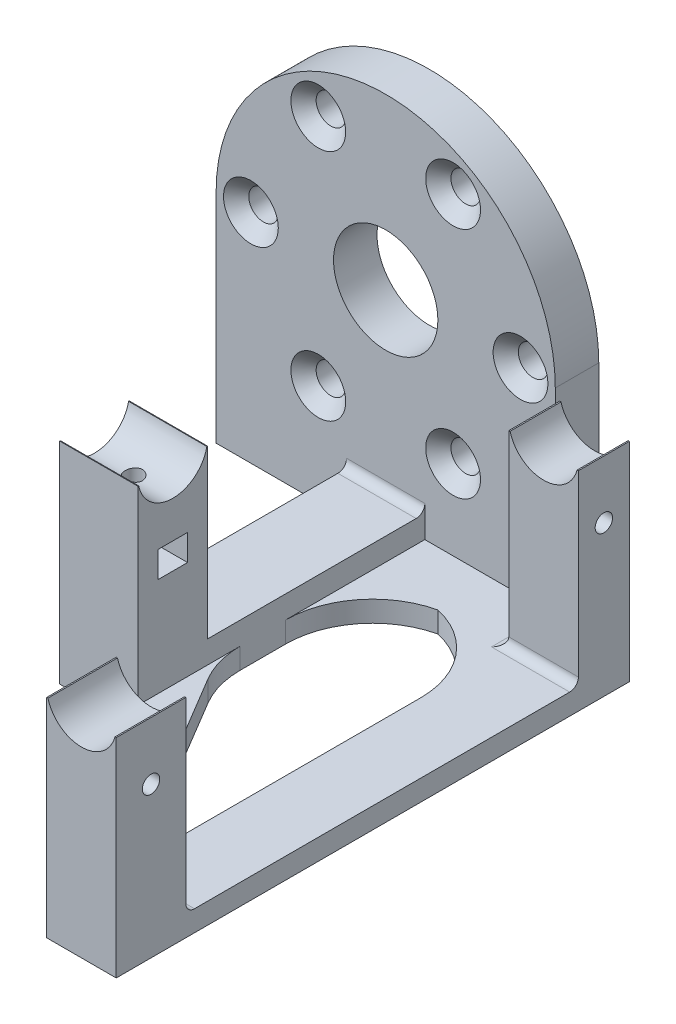
SolidWorks part; units mm, degrees
ref_plane "Front Plane" through (0, 0, 0) normal (0, 0, 1) x (1, 0, 0)
ref_plane "Top Plane" through (0, 0, 0) normal (0, 1, 0) x (1, 0, 0)
ref_plane "Right Plane" through (0, 0, 0) normal (1, 0, 0) x (0, 0, -1)
sketch "Sketch5" plane through (0, 0, 0) normal (0, 0, 1) x (1, 0, 0)
  line L0 (0, 0) -> (0, 15.5) construction
  circle A0 centre (0, 0) radius 19.5
  circle A1 centre (-7.75, 13.4234) radius 1.5
  circle A2 centre (0, 0) radius 6
  circle A3 centre (7.75, 13.4234) radius 1.5
  circle A4 centre (15.5, 0) radius 1.5
  circle A5 centre (7.75, -13.4234) radius 1.5
  circle A6 centre (-7.75, -13.4234) radius 1.5
  circle A7 centre (-15.5, 0) radius 1.5
  point P18 (0, 0)
  dimension "D2" = 3
  dimension "D3" = 39
  dimension "D4" = 12
  dimension "D1" = 15.5
  dimension "D5" = 6
extrude "Boss-Extrude1" add sketch "Sketch5" along normal blind 5
hole_wizard "CSK for M3 Flat Head Machine Screw1" positions "Sketch7" profile "Sketch6" countersink size "M3" standard "ANSI Metric" end condition through all
sketch "Sketch7" plane through (0, 0, 5) normal (0, 0, 1) x (1, 0, 0)
  point P0 (-15.5, 0)
  point P3 (-7.75, 13.4234)
  point P6 (7.75, 13.4234)
  point P9 (15.5, 0)
  point P12 (7.75, -13.4234)
  point P15 (-7.75, -13.4234)
sketch "Sketch6" plane through (-15.5, 0, 5) normal (1, 0, 0) x (0, -1, 0)
  line L0 (0, 0) -> (0, 5)
  line L1 (0, 5) -> (1.7, 5)
  line L2 (1.7, 5) -> (1.7, 1.45)
  line L3 (1.7, 1.45) -> (3.15, 0)
  line L5 (3.15, 0) -> (0, 0)
  line L6 (-1.7, 1.45) -> (-3.15, 0) construction
  line L11 (0, -6.35) -> (0, 107.95) construction
  dimension "Thru Hole Dia." = 3.4
  dimension "Thru Hole Depth" = 5
  dimension "Near C'Sink Dia." = 6.3
  dimension "Near C'Sink Angle" = 90
sketch "Sketch8" plane through (0, 0, 5) normal (0, 0, 1) x (1, 0, 0)
  line L0 (-19.5, 0) -> (-19.5, -25)
  line L1 (-19.5, -25) -> (19.5, -25)
  line L2 (19.5, -25) -> (19.5, 0)
  circle A0 centre (0, 0) radius 19.5 construction
  arc A1 (-19.5, 0) -> (19.5, 0) centre (0, 0) ccw
  dimension "D1" = 25
extrude "Boss-Extrude2" add sketch "Sketch8" against normal up to surface (5 mm away) up to face at (-13.8, 0, 0)
sketch "Sketch9" plane through (0, 0, 5) normal (0, 0, 1) x (1, 0, 0)
  line L0 (-19.5, -25) -> (19.5, -25) construction
  line L4 (-4.5, -20) -> (-4.5, -25)
  line L5 (4.5, -20) -> (-4.5, -25) construction
  line L6 (4.5, -25) -> (-4.5, -20) construction
  line L7 (-19.5, -25) -> (0, -22.5) construction
  line L8 (0, -22.5) -> (19.5, -25) construction
  line L9 (-4.5, -25) -> (4.5, -25)
  line L10 (-4.5, -20) -> (4.5, -20)
  line L11 (4.5, -20) -> (4.5, -25)
  point P0 (0, -22.5)
  dimension "D1" = 5
  dimension "D2" = 9
extrude "Boss-Extrude3" add sketch "Sketch9" along normal blind 32.9817
sketch "Sketch10" plane through (0.3712, -20, 0) normal (0, 1, 0) x (1, 0, 0)
  line L1 (-4.8712, -37.9817) -> (4.1288, -37.9817)
  line L2 (-4.8712, -37.9817) -> (-4.8712, -29.9817)
  line L3 (-4.8712, -29.9817) -> (4.1288, -29.9817)
  line L4 (4.1288, -37.9817) -> (4.1288, -29.9817)
  line L6 (-4.8712, -37.9817) -> (-4.8712, -5) construction
  line L7 (4.1288, -37.9817) -> (4.1288, -5) construction
  dimension "D1" = 8
extrude "Boss-Extrude4" add sketch "Sketch10" along normal blind 24
sketch "Sketch11" plane through (-4.5, 0, 0) normal (-1, 0, 0) x (0, 0, 1)
  line L0 (29.9817, 4) -> (29.9817, -20) construction
  line L2 (29.9817, 4) -> (37.9817, 4) construction
  line L3 (37.9817, 4) -> (37.9817, -25) construction
  line L4 (29.9817, 0) -> (27.1369, 2.0822)
  line L5 (27.1369, 2.0822) -> (27.3574, 4.8482)
  line L6 (27.3574, 4.8482) -> (32.7492, 5.4696)
  line L7 (32.7492, 5.4696) -> (41.4483, 5.0286)
  line L8 (41.4483, 5.0286) -> (40.8237, 2.383)
  line L9 (40.8237, 2.383) -> (37.9817, 0)
  line L10 (29.9817, -0.8) -> (30.0625, -0.8)
  line L11 (37.9009, -0.8) -> (37.9817, -0.8)
  line L12 (37.9817, 0) -> (37.9817, -0.8)
  line L13 (29.9817, -0.8) -> (29.9817, 0)
  arc A0 (30.0625, -0.8) -> (37.9009, -0.8) centre (33.9817, 0) ccw
  dimension "D1" = 0.8
extrude "Cut-Extrude1" cut sketch "Sketch11" against normal blind 20
sketch "Sketch12" plane through (0, -0.8, 0) normal (0, 1, 0) x (1, 0, 0)
  line L0 (-4.5, -29.9817) -> (4.5, -37.9817) construction
  line L1 (4.5, -29.9817) -> (-4.5, -37.9817) construction
  line L2 (4.5, -37.9009) -> (4.5, -30.0625) construction
  line L3 (4.5, -29.9817) -> (4.5, -5) construction
  circle A0 centre (0, -33.9817) radius 1
  dimension "D1" = 2
extrude "Cut-Extrude2" cut sketch "Sketch12" against normal blind 16
sketch "Sketch13" plane through (-4.5, 0, 0) normal (-1, 0, 0) x (0, 0, 1)
  line L0 (29.9817, -8.9707) -> (32.2817, -8.9707) construction
  line L1 (32.2817, -8.2443) -> (35.6817, -8.2443)
  line L2 (32.2817, -8.2443) -> (32.2817, -11.2443)
  line L3 (32.2817, -11.2443) -> (35.6817, -11.2443)
  line L4 (35.6817, -8.2443) -> (35.6817, -11.2443)
  line L5 (29.9817, -0.8) -> (29.9817, -20) construction
  line L6 (37.9817, -0.8) -> (37.9817, -25) construction
  line L7 (35.6817, -8.9707) -> (37.9817, -8.9707) construction
  dimension "D1" = 3.4
  dimension "D2" = 3
extrude "Cut-Extrude3" cut sketch "Sketch13" against normal up to surface (9 mm away) up to face at (4.5, -12.05, 26.7363)
sketch "Sketch14" plane through (0, -25, 0) normal (0, -1, 0) x (1, 0, 0)
  line L0 (4.5, 37.9817) -> (4.5, 5) construction
  line L1 (4.5, 5) -> (28.015, 5)
  line L2 (4.5, 5) -> (4.5, 11)
  line L3 (4.5, 11) -> (20.015, 11)
  line L4 (28.015, 5) -> (28.015, 12.4921)
  line L5 (28.015, -11.9618) -> (28.015, 22.5232) construction
  line L6 (20.015, 70.0082) -> (20.015, 35.5232) construction
  line L8 (28.015, 12.4921) -> (28.015, 64)
  line L9 (28.015, 64) -> (20.015, 64)
  line L10 (20.015, 11) -> (20.015, 64)
  line L12 (4.5, 5) -> (19.5, 5) construction
  dimension "D1" = 0
  dimension "D2" = 6
  dimension "D3" = 59
extrude "Boss-Extrude5" add sketch "Sketch14" against normal blind 2.4
sketch "Sketch15" plane through (28.015, 0, 0) normal (1, 0, 0) x (0, 0, -1)
  line L0 (-38.5232, 4) -> (-70.0082, 4) construction
  line L1 (-64, -22.6) -> (-56, -22.6)
  line L2 (-64, -22.6) -> (-64, 4)
  line L3 (-64, 4) -> (-56, 4)
  line L4 (-56, -22.6) -> (-56, 4)
  line L6 (-5, -22.6) -> (-13, -22.6)
  line L7 (-5, -22.6) -> (-5, 4)
  line L8 (-5, 4) -> (-13, 4)
  line L9 (-13, -22.6) -> (-13, 4)
  dimension "D1" = 8
extrude "Boss-Extrude6" add sketch "Sketch15" against normal up to surface (8 mm away) up to face at (20.015, -23.8, 37.5)
sketch "Sketch16" plane through (0, 0, 64) normal (0, 0, 1) x (1, 0, 0)
  line L0 (20.015, -1.0579) -> (20.1574, -1.0579)
  line L1 (20.015, 4) -> (20.015, -25) construction
  line L2 (28.015, 4) -> (28.015, -25) construction
  line L3 (28.015, -1.0579) -> (30.9797, 0.9089)
  line L4 (30.9797, 0.9089) -> (30.0419, 7.8056)
  line L5 (20.015, -1.0579) -> (20.015, 10.6199)
  line L6 (20.015, 5.7446) -> (20.015, 15.4952) construction
  line L7 (20.015, 10.6199) -> (30.0419, 7.8056)
  line L8 (27.8726, -1.0579) -> (28.015, -1.0579)
  arc A0 (20.1574, -1.0579) -> (27.8726, -1.0579) centre (24.015, 0) ccw
extrude "Cut-Extrude4" cut sketch "Sketch16" against normal up to surface (59 mm away) up to face at (22.51, -14.5333, 5)
sketch "Sketch17" plane through (0, -22.6, 0) normal (0, 1, 0) x (1, 0, 0)
  line L0 (20.015, -56) -> (20.015, -13) construction
  line L1 (20.015, -13.8581) -> (28.015, -13.8581)
  line L2 (20.015, -13.8581) -> (20.015, -10.8581)
  line L3 (20.015, -10.8581) -> (28.015, -10.8581)
  line L4 (28.015, -13.8581) -> (28.015, -10.8581)
  line L5 (28.015, -5) -> (28.015, -13) construction
  dimension "D1" = 3
extrude "Cut-Extrude5" cut sketch "Sketch17" along normal up to surface (21.5421 mm away) up to face at (20.0862, -1.0579, 9)
sketch "Sketch19" plane through (0, 0, 29.9817) normal (0, 0, -1) x (-1, 0, 0)
  circle A0 centre (-7.75, -13.4234) radius 3
  dimension "D1" = 6
extrude "Cut-Extrude6" [suppressed] cut sketch "Sketch19" against normal through all
sketch "Sketch20" plane through (0, -22.6, 0) normal (0, 1, 0) x (1, 0, 0)
  line L0 (20.015, -64) -> (4.5, -37.9817)
  line L1 (20.015, -55) -> (4.5, -28.9817)
  line L2 (20.015, -56) -> (20.015, -11) construction
  line L3 (4.5, -29.9817) -> (4.5, -5) construction
  line L4 (4.5, -28.9817) -> (4.5, -37.9817)
  line L5 (20.015, -55) -> (20.015, -64)
  dimension "D1" = 9
extrude "Boss-Extrude7" add sketch "Sketch20" against normal up to surface (2.4 mm away) up to face at (8.005, -25, 20.4969)
fillet "Fillet1" radius 10 3 edges at (20.015, -23.8, 11) (4.5, -23.8, 11) (4.5, -23.8, 28.9817)
fillet "Fillet2" radius 1 1 edges at (20.015, -23.8, 55)
fillet "Fillet3" radius 1 5 edges at (0, -20, 5) (20.015, -22.6, 60) (20.015, -22.6, 7.9291) (24.015, -22.6, 10.8581) (24.015, -22.6, 56)
sketch "Sketch22" plane through (28.015, 0, 0) normal (1, 0, 0) x (0, 0, -1)
  circle A0 centre (-60, -7.7015) radius 1
extrude "Cut-Extrude7" cut sketch "Sketch22" against normal up to surface (8 mm away) up to face at (20.015, -11.329, 60)
sketch "Sketch23" plane through (28.015, 0, 0) normal (1, 0, 0) x (0, 0, -1)
  circle A0 centre (-7.9291, -7.7015) radius 1
extrude "Cut-Extrude8" cut sketch "Sketch23" against normal up to surface (8 mm away) up to face at (20.015, -11.329, 7.9291)
